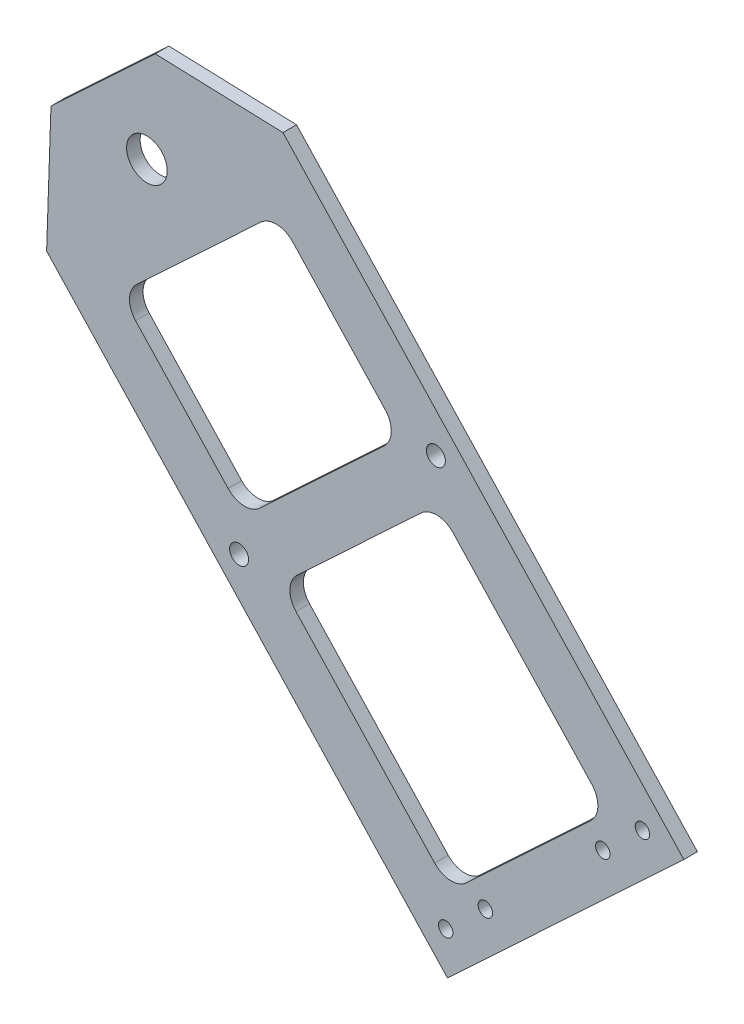
SolidWorks part; units mm, degrees
material "Thornel Mat VMA"
ref_plane "前视基准面" through (0, 0, 0) normal (0, 0, 1) x (1, 0, 0)
ref_plane "上视基准面" through (0, 0, 0) normal (0, 1, 0) x (1, 0, 0)
ref_plane "右视基准面" through (0, 0, 0) normal (1, 0, 0) x (0, 0, -1)
sketch "草图1" plane through (0, 0, 0) normal (0, 0, 1) x (1, 0, 0)
  line L0 (-324.626, -164.0776) -> (-272.3024, -115.2022)
  line L1 (-324.626, -164.0776) -> (-413.3663, -69.0768)
  line L2 (-272.3024, -115.2022) -> (-361.0428, -20.2014)
  line L3 (-412.4031, -40.8089) -> (-389.3106, -19.2382)
  line L4 (-320.3942, -143.7038) -> (-292.917, -118.0374)
  line L5 (-327.4612, -143.463) -> (-358.179, -110.5781)
  line L6 (-292.6763, -110.9704) -> (-323.3941, -78.0855)
  line L7 (-357.9382, -103.5112) -> (-330.461, -77.8447)
  line L8 (-366.1296, -94.7419) -> (-338.6524, -69.0754)
  line L9 (-373.1966, -94.5011) -> (-393.6751, -72.5778)
  line L10 (-338.4117, -62.0084) -> (-358.8902, -40.0852)
  line L11 (-393.4343, -65.5108) -> (-365.9572, -39.8444)
  line L12 (-413.3663, -69.0768) -> (-412.4031, -40.8089)
  line L13 (-361.0428, -20.2014) -> (-389.3106, -19.2382)
  line L14 (-325.0196, -154.8665) -> (-281.4654, -114.1824) construction
  arc A0 (-292.917, -118.0374) -> (-292.6763, -110.9704) centre (-296.3301, -114.3835) ccw
  arc A1 (-327.4612, -143.463) -> (-320.3942, -143.7038) centre (-323.8073, -140.0499) ccw
  arc A2 (-323.3941, -78.0855) -> (-330.461, -77.8447) centre (-327.0479, -81.4986) ccw
  arc A3 (-358.179, -110.5781) -> (-357.9382, -103.5112) centre (-354.5251, -107.165) cw
  circle A4 centre (-327.2008, -65.2205) radius 2.1 construction
  circle A5 centre (-370.755, -105.9045) radius 2.1 construction
  circle A6 centre (-327.2008, -65.2205) radius 2.1
  circle A7 centre (-370.755, -105.9045) radius 2.1
  arc A8 (-358.8902, -40.0852) -> (-365.9572, -39.8444) centre (-362.5441, -43.4983) ccw
  arc A9 (-338.6524, -69.0754) -> (-338.4117, -62.0084) centre (-342.0655, -65.4215) ccw
  arc A10 (-373.1966, -94.5011) -> (-366.1296, -94.7419) centre (-369.5427, -91.088) ccw
  arc A11 (-393.6751, -72.5778) -> (-393.4343, -65.5108) centre (-390.0212, -69.1647) cw
  circle A12 centre (-391.1637, -40.4006) radius 4.5
  circle A13 centre (-325.0196, -154.8665) radius 1.6
  circle A14 centre (-316.2503, -146.6751) radius 1.6
  circle A15 centre (-290.2347, -122.3739) radius 1.6
  circle A16 centre (-281.4654, -114.1824) radius 1.6
  point P4 (-374.6951, -5.5859)
  point P5 (-427.0187, -54.4613)
  point P20 (-289.2632, -114.6243)
  point P25 (-326.8071, -74.4316)
  point P36 (-362.3033, -36.4313)
  point P39 (-334.9986, -65.6623)
  dimension "D10" = 5
  dimension "D11" = 5
  dimension "D14" = 9
  dimension "D15" = 3.2
  dimension "D19" = 6
  dimension "D20" = 6
  dimension "D1" = 150
  dimension "D2" = 12
  dimension "D3" = 12
  dimension "D4" = 12
  dimension "D5" = 12
  dimension "D6" = 12
  dimension "D7" = 12
  dimension "D8" = 55
  dimension "D9" = 40
  dimension "D16" = 7
  dimension "D17" = 12
  dimension "D18" = 12
extrude "凸台-拉伸1" add sketch "草图1" along normal blind 3
